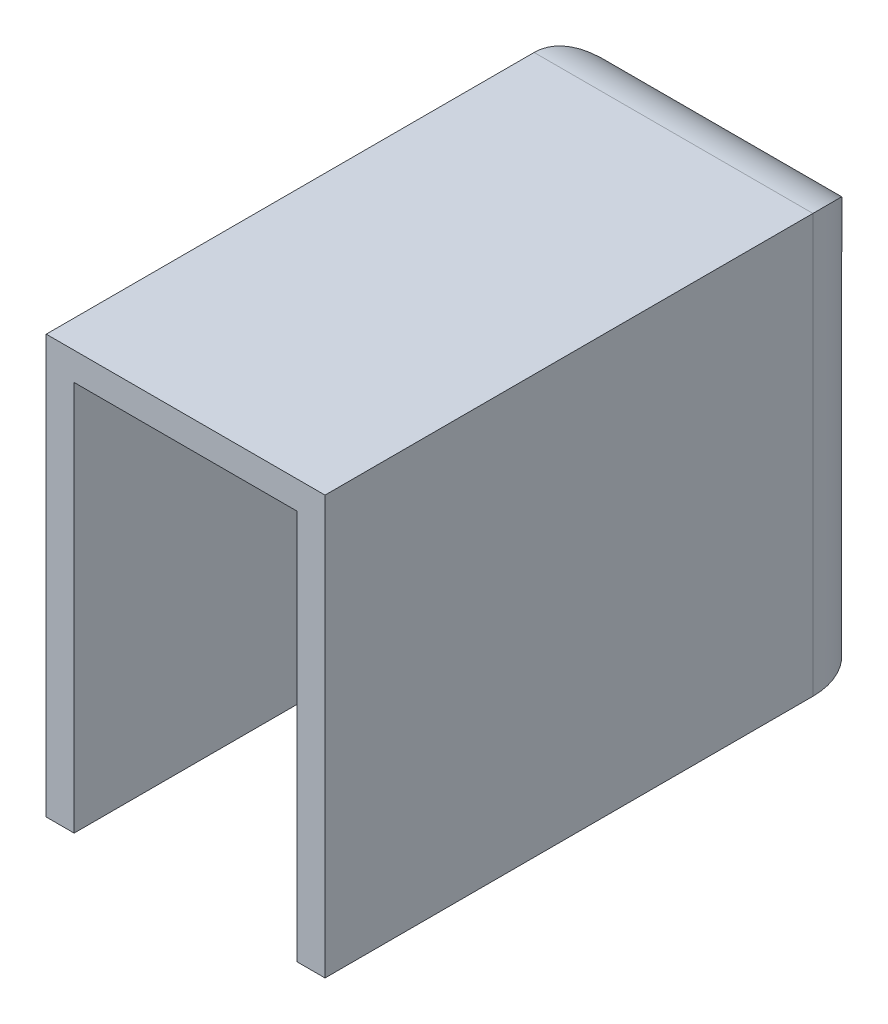
SolidWorks part; units mm, degrees
ref_plane "Płaszczyzna przednia" through (0, 0, 0) normal (0, 0, 1) x (1, 0, 0)
ref_plane "Płaszczyzna górna" through (0, 0, 0) normal (0, 1, 0) x (1, 0, 0)
ref_plane "Płaszczyzna prawa" through (0, 0, 0) normal (1, 0, 0) x (0, 0, -1)
sketch "Szkic1" plane through (0, 0, 0) normal (0, 0, 1) x (1, 0, 0)
  line L1 (-10, -15) -> (10, -15)
  line L2 (-10, -15) -> (-10, 15)
  line L3 (-10, 15) -> (10, 15)
  line L4 (10, -15) -> (10, 15)
  line L5 (-10, -15) -> (10, 15) construction
  line L6 (-10, 15) -> (10, -15) construction
  point P0 (0, 0)
  dimension "D1" = 20
  dimension "D2" = 30
extrude "Dodanie-wyciągnięcie1" add sketch "Szkic1" along normal blind 40
shell "Skorupa3" thickness 2 removed face at (0, 0, 40) removed face at (0, -15, 20)
fillet "Zaokrąglenie1" radius 5 3 edges at (-10, 0, 0) (0, 15, 0) (10, 0, 0)
sketch "Szkic2" plane through (0, 0, 2) normal (0, 0, 1) x (1, 0, 0)
  line L0 (-8, -15) -> (8, -15) construction
  line L1 (6, -10) -> (-6, -10)
  line L2 (6, -10) -> (6, -12)
  line L3 (6, -12) -> (-6, -12)
  line L4 (-6, -10) -> (-6, -12)
  line L5 (6, -10) -> (-6, -12) construction
  line L6 (6, -12) -> (-6, -10) construction
  line L7 (8, -15) -> (8, 13) construction
  point P0 (0, -11)
  dimension "D1" = 3
  dimension "D2" = 2
  dimension "D3" = 12
  dimension "D4" = 2
extrude "Dodanie-wyciągnięcie2" add sketch "Szkic2" along normal blind 2.5
sketch "Szkic3" plane through (-10, 0, 0) normal (-1, 0, 0) x (0, 0, 1)
  line L0 (22.5, -7.3126) -> (22.5, 5.7112) construction
  text T0 "<b>GE</b>" font "Arial" height 5
extrude "Wytnij-wyciągnięcie2" cut sketch "Szkic3" against normal blind 8
